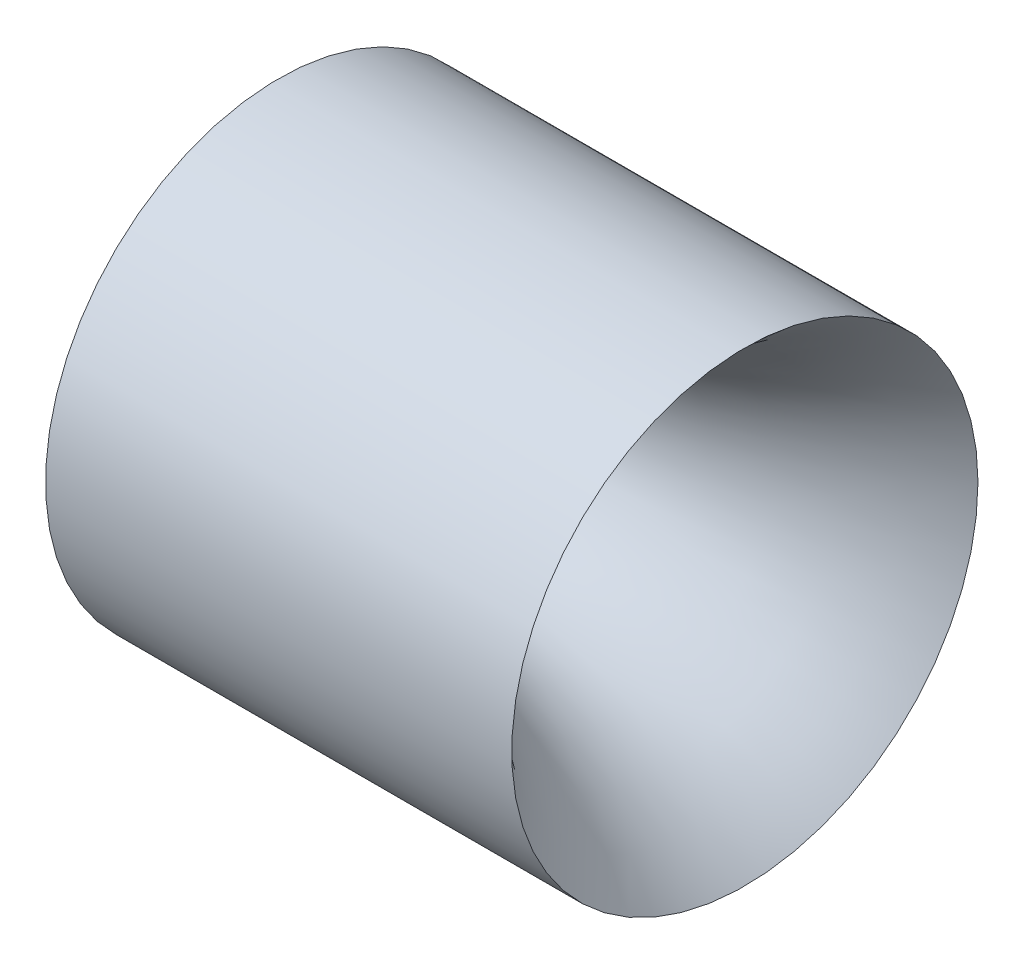
SolidWorks part; units mm, degrees
ref_plane "Plan de face" through (0, 0, 0) normal (0, 0, 1) x (1, 0, 0)
ref_plane "Plan de dessus" through (0, 0, 0) normal (0, 1, 0) x (1, 0, 0)
ref_plane "Plan de droite" through (0, 0, 0) normal (1, 0, 0) x (0, 0, -1)
sketch "Esquisse3" plane through (0, 0, 0) normal (1, 0, 0) x (0, 0, -1)
  circle A0 centre (0, 0) radius 5
  circle A1 centre (0, 0) radius 2.2
extrude "Boss.-Extru.2" add sketch "Esquisse3" along normal blind 10
fillet "Congé1" radius 10 1 edges at (10, 0, -2.2)
